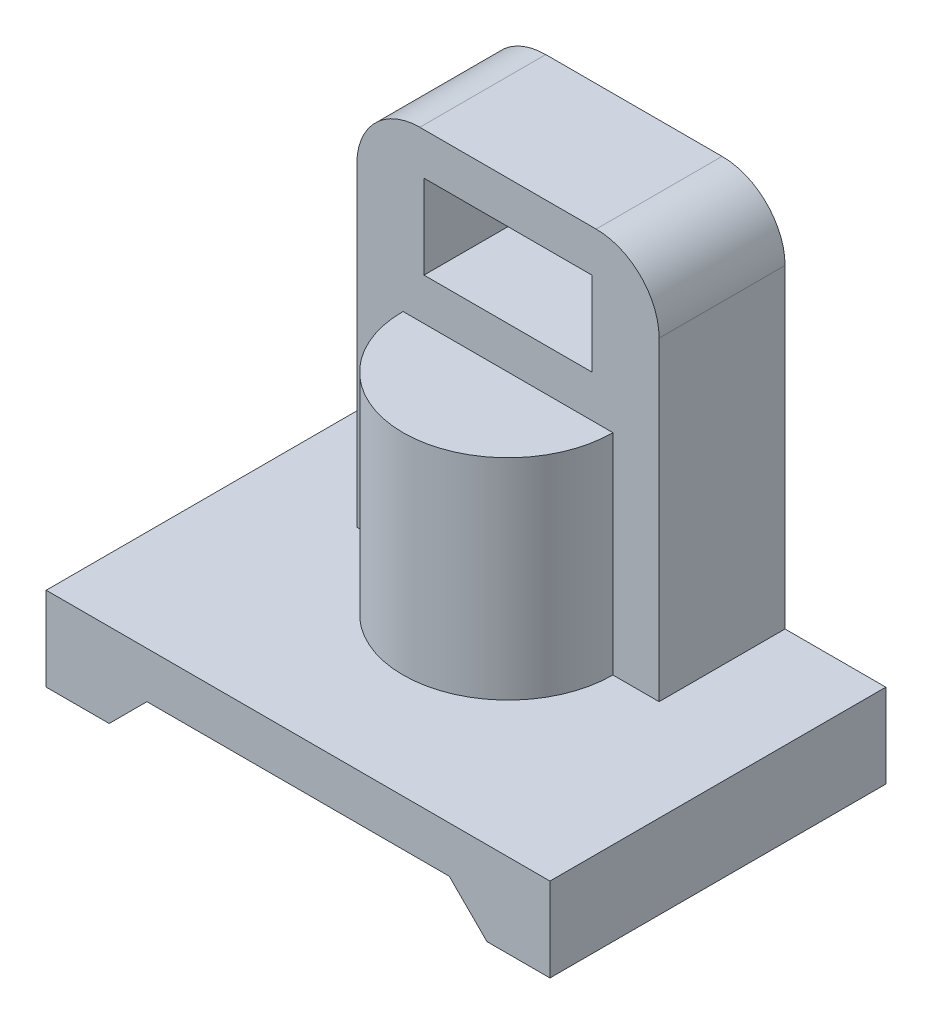
SolidWorks part; units mm, degrees
ref_plane "前视基准面" through (0, 0, 0) normal (0, 0, 1) x (1, 0, 0)
ref_plane "上视基准面" through (0, 0, 0) normal (0, 1, 0) x (1, 0, 0)
ref_plane "右视基准面" through (0, 0, 0) normal (1, 0, 0) x (0, 0, -1)
other "Configuration Table"
sketch "草图1" plane through (0, 0, 0) normal (0, 1, 0) x (1, 0, 0)
  line L0 (0, 0) -> (0, -80)
  line L1 (0, -80) -> (120, -80)
  line L2 (120, -80) -> (120, 0)
  line L3 (120, 0) -> (0, 0)
  dimension "D1" = 120
  dimension "D2" = 80
extrude "凸台-拉伸1" add sketch "草图1" along normal blind 20
sketch "草图2" plane through (0, 0, 80) normal (0, 0, 1) x (1, 0, 0)
  line L0 (60, 0) -> (105, 0)
  line L1 (0, 0) -> (120, 0) construction
  line L2 (105, 0) -> (96, 9)
  line L3 (96, 9) -> (57.0058, 9)
  line L4 (57.0058, 9) -> (24, 9)
  line L5 (24, 9) -> (15, 0)
  line L6 (15, 0) -> (60, 0)
  dimension "D1" = 45
  dimension "D2" = 45
  dimension "D3" = 45
  dimension "D4" = 45
  dimension "D5" = 9
extrude "切除-拉伸1" cut sketch "草图2" against normal through all both and the other way through all
sketch "草图3" plane through (0, 20, 0) normal (0, 1, 0) x (1, 0, 0)
  line L0 (120, 0) -> (0, 0) construction
  line L1 (60, 0) -> (24, 0)
  line L2 (24, 0) -> (24, -30)
  line L3 (24, -30) -> (49.6734, -30)
  line L4 (49.6734, -30) -> (96, -30)
  line L5 (96, -30) -> (96, 0)
  line L6 (96, 0) -> (60, 0)
  line L7 (60, 0) -> (60, -30)
  line L8 (40, 0) -> (40, -30)
  line L9 (80, 0) -> (80, -30)
  arc A0 (35, -30) -> (85, -30) centre (60, -30) ccw
  line M7 (120, 0) -> (0, 0)
  dimension "D4" = 25
  dimension "D1" = 30
  dimension "D2" = 36
  dimension "D3" = 36
  dimension "D5" = 16
extrude "凸台-拉伸2" add sketch "草图3" along normal blind 90 contours L8 L1 L2 L3 | L9 L4 L5 M7 | L6 L1 L2 L3 L4 L5 region at (32, 20, 15) region at (88, 20, 15)
extrude "凸台-拉伸3" add sketch "草图3<3>" along normal blind 50 contours L3 A0 L4 region at (60, 20, 40.6103)
sketch "草图3<3>" plane through (0, 20, 0) normal (0, 1, 0) x (1, 0, 0) same geometry as "草图3"
fillet "圆角1" radius 15 2 edges at (96, 110, 15) (24, 110, 15)
sketch "草图5" plane through (0, 0, 30) normal (0, 0, 1) x (1, 0, 0)
  line L6 (39, 110) -> (81, 110) construction
  line L7 (60, 110) -> (60, 59.5479) construction
  line L8 (40, 100) -> (80, 100)
  line L9 (80, 100) -> (80, 80)
  line L10 (80, 80) -> (40, 80)
  line L11 (105, 0) -> (120, 0) construction
  line L12 (40, 100) -> (40, 80)
  point P11 (60, 80)
  point P12 (60, 100)
  dimension "D1" = 20
  dimension "D2" = 20
  dimension "D3" = 80
extrude "切除-拉伸2" cut sketch "草图5" against normal through all both and the other way through all
